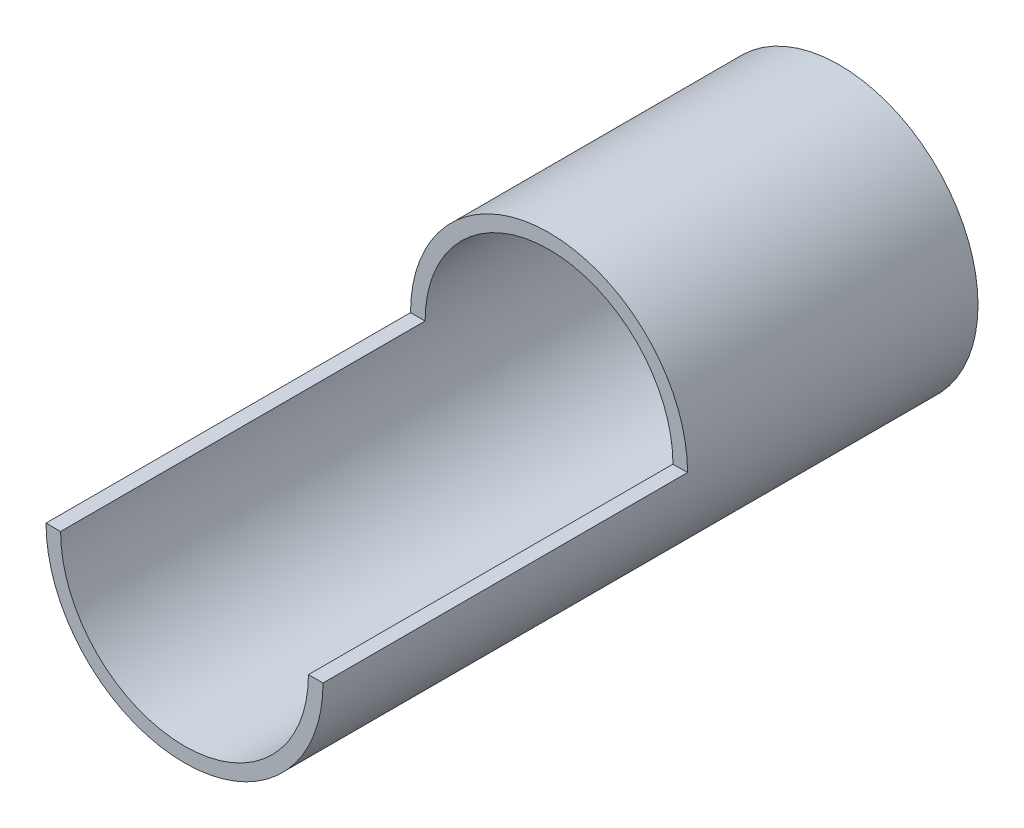
SolidWorks part; units mm, degrees
ref_plane "Front Plane" through (0, 0, 0) normal (0, 0, 1) x (1, 0, 0)
ref_plane "Top Plane" through (0, 0, 0) normal (0, 1, 0) x (1, 0, 0)
ref_plane "Right Plane" through (0, 0, 0) normal (1, 0, 0) x (0, 0, -1)
sketch "Sketch1" plane through (0, 0, 0) normal (0, 0, 1) x (1, 0, 0)
  circle A0 centre (0, 0) radius 24.13
  circle A1 centre (0, 0) radius 21.59
  dimension "D1" = 48.26
  dimension "D2" = 2.54
extrude "Boss-Extrude1" add sketch "Sketch1" along normal blind 114.1
sketch "Sketch3" plane through (0, 0, 114.1) normal (0, 0, 1) x (1, 0, 0)
  line L1 (24.13, 0) -> (-24.13, 0)
  line L2 (24.13, 0) -> (24.13, 24.13)
  line L3 (24.13, 24.13) -> (-24.13, 24.13)
  line L4 (-24.13, 0) -> (-24.13, 24.13)
  circle A0 centre (0, 0) radius 24.13 construction
extrude "Cut-Extrude1" cut sketch "Sketch3" against normal blind 63.5
equation "\"FoamCore\" = \".2\""
equation "\"MDF\" = \".2\""
equation "\"GMaterial\"= \".2\""
equation "\"PVCMountDiameter\" = \"0.5in\""
equation "\"PVCMountDistanceToEdge\" = \"0.5\""
equation "\"BaseWidth\" = \"8in\""
equation "\"BaseLength\" = \"10in\""
equation "\"BallDiameter\" = \"38mm\""
equation "\"BaseGap\" = \"4in\""
equation "\"FunnelTopDiameter\" = \"8in\""
equation "\"FunnelTopDepth\" = \"0.5in\""
equation "\"BallGap\" = \"0.1in\""
equation "\"FunnelLength\" = 3in"
equation "\"FunnelMaterial\" = 0.1in"
equation "\"FunnelLowerDiameter\" = 1.9in"
equation "\"FunnelDepth\" = 1.5in"
equation "\"D1@Sketch1\"=\"FunnelLowerDiameter\""
equation "\"D2@Sketch1\"=\"FunnelMaterial\""
equation "\"D1@Boss-Extrude1\"=\"AmmoFeederLength\""
equation "\"PVCThickness\" = \"0.13in\""
equation "\"AmmoFeederLength\" = 1.5in + 76mm"
equation "\"AmmoFeederCutoffLength\"= \"MovingWheelDiameter\""
equation "\"D1@Cut-Extrude1\"=\"AmmoFeederCutoffLength\""
